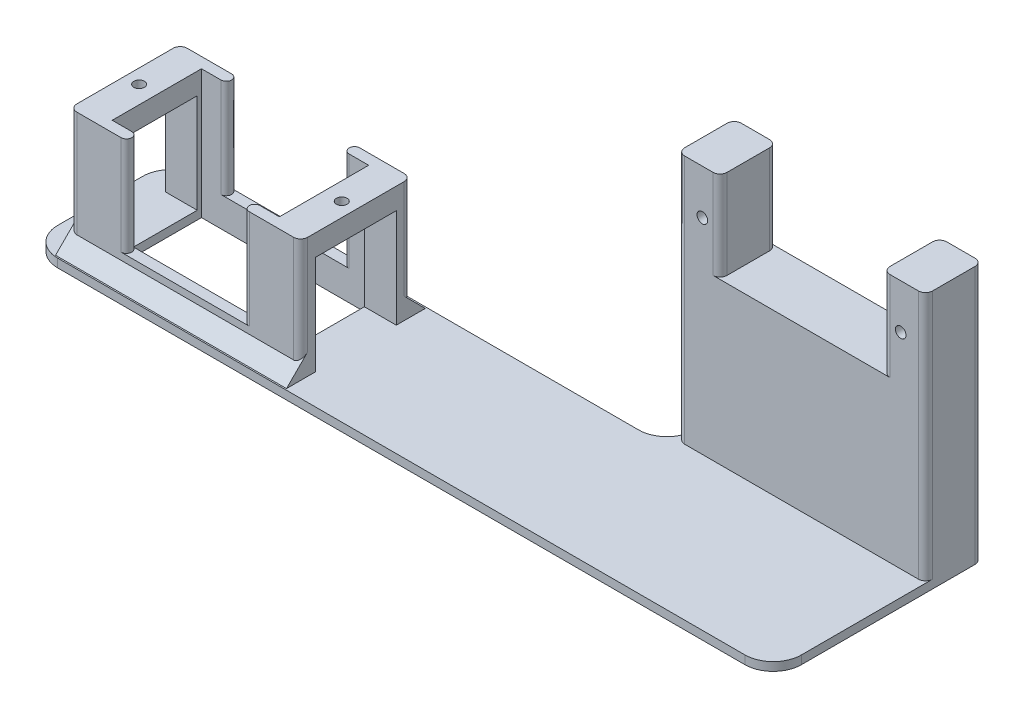
SolidWorks part; units mm, degrees
ref_plane "Plano frontal" through (0, 0, 0) normal (0, 0, 1) x (1, 0, 0)
ref_plane "Plano superior" through (0, 0, 0) normal (0, 1, 0) x (1, 0, 0)
ref_plane "Plano direito" through (0, 0, 0) normal (1, 0, 0) x (0, 0, -1)
sketch "Esboço1" plane through (0, 0, 0) normal (0, 1, 0) x (1, 0, 0)
  line L0 (-35.1312, 0) -> (39.0565, 0) construction
  line L1 (-52.5, -10) -> (52.5, -10)
  line L2 (-52.5, -10) -> (-52.5, 10)
  line L3 (-52.5, 10) -> (52.5, 10)
  line L4 (52.5, -10) -> (52.5, 10)
  line L5 (-52.5, -10) -> (52.5, 10) construction
  line L6 (-52.5, 10) -> (52.5, -10) construction
  line L8 (52.5, 10) -> (17.5, 10)
  line L9 (52.5, 10) -> (52.5, 19.5)
  line L10 (52.5, 19.5) -> (17.5, 19.5)
  line L11 (17.5, 10) -> (17.5, 19.5)
  point P0 (0, 0)
  dimension "D1" = 20
  dimension "D2" = 105
  dimension "D3" = 35
  dimension "D4" = 9.5
extrude "Base" add sketch "Esboço1" along normal blind 1.2 contours L11 L3 L9 L10 | L1 L4 L3 L2 region at (0, 0, 0) region at (35, 0, -14.75)
sketch "Esboço2" plane through (0, 1.2, 0) normal (0, 1, 0) x (1, 0, 0)
  line L0 (-51.7316, 0) -> (51.4564, 0) construction
  line L2 (-49, -7.8) -> (-16.4, -7.8)
  line L3 (-49, -7.8) -> (-49, 7.8)
  line L4 (-49, 7.8) -> (-16.4, 7.8)
  line L5 (-16.4, -7.8) -> (-16.4, 7.8)
  line L6 (-49, -7.8) -> (-16.4, 7.8) construction
  line L7 (-49, 7.8) -> (-16.4, -7.8) construction
  line L8 (-52.5, -10) -> (-52.5, 10) construction
  point P3 (-32.7, 0)
  dimension "D1" = 15.6
  dimension "D2" = 32.6
  dimension "D3" = 19.8
extrude "Suporte 1" add sketch "Esboço2" along normal blind 17 contours L4 L5 L2 L3
sketch "Esboço3" plane through (0, 18.2, 0) normal (0, 1, 0) x (1, 0, 0)
  line L0 (-41.688, 0) -> (-10.1812, 0) construction
  line L1 (-32.7, 8.1862) -> (-32.7, -8.1862) construction
  line L2 (-52.5, 10) -> (17.5, 10) construction
  line L3 (-44.5, -6.3) -> (-20.9, -6.3)
  line L4 (-44.5, -6.3) -> (-44.5, 6.3)
  line L5 (-44.5, 6.3) -> (-20.9, 6.3)
  line L6 (-20.9, -6.3) -> (-20.9, 6.3)
  line L7 (-44.5, -6.3) -> (-20.9, 6.3) construction
  line L8 (-44.5, 6.3) -> (-20.9, -6.3) construction
  line L9 (-52.5, -10) -> (-52.5, 10) construction
  point P5 (-32.7, 0)
  point P10 (0, 0)
  dimension "D1" = 23.6
  dimension "D2" = 12.6
  dimension "D3" = 10
  dimension "D4" = 19.8
extrude "Corte-extrusão1" cut sketch "Esboço3" against normal blind 19.5
sketch "Esboço4" plane through (0, 0, 7.8) normal (0, 0, 1) x (1, 0, 0)
  line L0 (-32.7, 25.969) -> (-32.7, -6.8255) construction
  line L1 (-52.5, 1.2) -> (-52.5, 0) construction
  line L3 (-41, 4.2) -> (-24.4, 4.2)
  line L4 (-41, 4.2) -> (-41, 21.4379)
  line L5 (-41, 21.4379) -> (-24.4, 21.4379)
  line L6 (-24.4, 4.2) -> (-24.4, 21.4379)
  line L7 (-41, 4.2) -> (-24.4, 21.4379) construction
  line L8 (-41, 21.4379) -> (-24.4, 4.2) construction
  line L10 (-49, 1.2) -> (-16.4, 1.2) construction
  point P4 (-32.7, 12.8189)
  dimension "D1" = 19.8
  dimension "D2" = 16.6
  dimension "D3" = 3
extrude "Corte-extrusão2" cut sketch "Esboço4" against normal blind 19.5
sketch "Esboço5" plane through (-16.4, 0, 0) normal (1, 0, 0) x (0, 0, -1)
  line L0 (0, 18.8039) -> (0, -2.4039) construction
  line L1 (-7.8, 1.2) -> (7.8, 1.2) construction
  line L2 (-5.7, 1.2) -> (5.7, 1.2)
  line L3 (-5.7, 1.2) -> (-5.7, 15.2)
  line L4 (-5.7, 15.2) -> (5.7, 15.2)
  line L5 (5.7, 1.2) -> (5.7, 15.2)
  line L6 (-5.7, 1.2) -> (5.7, 15.2) construction
  line L7 (-5.7, 15.2) -> (5.7, 1.2) construction
  line L8 (-7.8, 18.2) -> (7.8, 18.2) construction
  point P3 (0, 8.2)
  dimension "D1" = 11.4
  dimension "D2" = 0
  dimension "D3" = 3
extrude "Corte-extrusão3" cut sketch "Esboço5" against normal blind 36.5
sketch "Esboço6" plane through (0, 18.2, 0) normal (0, 1, 0) x (1, 0, 0)
  line L0 (-8.0264, 0) -> (-42.894, 0) construction
  line L3 (-16.4, -7.8) -> (-16.4, 7.8) construction
  line L4 (-49, -7.8) -> (-49, 7.8) construction
  circle A0 centre (-47, 0) radius 0.75
  circle A1 centre (-18.4, 0) radius 0.75
  dimension "D1" = 1.5
  dimension "D2" = 1.5
  dimension "D3" = 2
  dimension "D4" = 2
extrude "Corte-extrusão4" cut sketch "Esboço6" against normal blind 7.5
sketch "Esboço7" plane through (0, 1.2, 0) normal (0, 1, 0) x (1, 0, 0)
  line L0 (35, 27.9686) -> (35, -20.0329) construction
  line L1 (-55.355, 0) -> (59.9055, 0) construction
  line L2 (52.5, 19.5) -> (17.5, 19.5) construction
  line L3 (17.5, 19.5) -> (52.5, 19.5)
  line L4 (17.5, 19.5) -> (17.5, 11.5)
  line L5 (17.5, 11.5) -> (52.5, 11.5)
  line L6 (52.5, 19.5) -> (52.5, 11.5)
  line L7 (17.5, 19.5) -> (52.5, 11.5) construction
  line L8 (17.5, 11.5) -> (52.5, 19.5) construction
  point P5 (35, 15.5)
  point P12 (35, 19.5)
  dimension "D1" = 35
  dimension "D2" = 0
  dimension "D3" = 8
  dimension "D4" = 11.5
extrude "Ressalto-extrusão3" add sketch "Esboço7" along normal blind 35.24
sketch "Esboço9" plane through (0, 0, -11.5) normal (0, 0, 1) x (1, 0, 0)
  line L0 (35, 36.44) -> (35, -1.0136) construction
  line L1 (17.5, 36.44) -> (52.5, 36.44) construction
  line L3 (23.5, 49.04) -> (46.5, 49.04)
  line L4 (23.5, 49.04) -> (23.5, 23.84)
  line L5 (23.5, 23.84) -> (46.5, 23.84)
  line L6 (46.5, 49.04) -> (46.5, 23.84)
  line L7 (23.5, 49.04) -> (46.5, 23.84) construction
  line L8 (23.5, 23.84) -> (46.5, 49.04) construction
  point P4 (35, 36.44)
  dimension "D1" = 0
  dimension "D2" = 25.2
  dimension "D3" = 23
extrude "Corte-extrusão5" cut sketch "Esboço9" against normal blind 22.5
sketch "Esboço10" plane through (0, 0, -11.5) normal (0, 0, 1) x (1, 0, 0)
  line L0 (13.6486, 30.14) -> (51.3481, 30.14) construction
  line L1 (23.5, 36.44) -> (23.5, 23.84) construction
  line L2 (46.5, 23.84) -> (46.5, 36.44) construction
  circle A0 centre (21, 30.14) radius 0.75
  circle A1 centre (49, 30.14) radius 0.75
  dimension "D1" = 2.5
  dimension "D2" = 2.5
  dimension "D3" = 1.5
  dimension "D4" = 1.5
extrude "Corte-extrusão6" cut sketch "Esboço10" against normal blind 22.5
chamfer "Chanfro1" distance 2 angle 45 1 edges at (-32.7, 1.2, 7.8)
chamfer "Chanfro2" distance 2 angle 45 1 edges at (-32.7, 1.2, -7.8)
fillet "Filete1" radius 1 1 edges at (52.5, 18.22, -19.5) type face fillet first side face at (52.5, 12.5467, -7) second side face at (49.75, 30.14, -19.5)
fillet "Filete2" radius 1 1 edges at (17.5, 18.22, -19.5) type face fillet first side face at (49.75, 30.14, -19.5) second side face at (17.5, 12.5467, -13.6667)
fillet "Filete3" radius 1 1 edges at (23.5, 30.14, -19.5) type face fillet first side face at (23.5, 30.14, -15.5) second side face at (49.75, 30.14, -19.5)
fillet "Filete4" radius 1 1 edges at (46.5, 30.14, -19.5) type face fillet first side face at (46.5, 30.14, -15.5) second side face at (49.75, 30.14, -19.5)
fillet "Filete5" radius 1 1 edges at (52.5, 18.82, -11.5) type face fillet first side face at (49.75, 30.14, -11.5) second side face at (52.5, 12.5467, -6.6667)
fillet "Filete6" radius 1 1 edges at (17.5, 18.82, -11.5) type face fillet first side face at (17.5, 12.5467, -13.3333) second side face at (49.75, 30.14, -11.5)
fillet "Filete7" radius 1 1 edges at (46.5, 30.14, -11.5) type face fillet first side face at (46.5, 30.14, -15) second side face at (49.75, 30.14, -11.5)
fillet "Filete8" radius 1 1 edges at (23.5, 30.14, -11.5) type face fillet first side face at (49.75, 30.14, -11.5) second side face at (23.5, 30.14, -15)
fillet "Filete9" 2 edges at (-41, 11.2, 7.8) (-41, 11.2, 6.3) type full round first side face at (-32.7, 10.95, 7.8) second side face at (-32.7, 10.15, 6.3) middle face at (-41, 11.2, 7.05)
fillet "Filete10" 2 edges at (-41, 11.2, -7.8) (-41, 11.2, -6.3) type full round first side face at (-32.7, 10.95, -7.8) second side face at (-32.7, 10.15, -6.3) middle face at (-41, 11.2, -7.05)
fillet "Filete11" 2 edges at (-24.4, 11.2, 6.3) (-24.4, 11.2, 7.8) type full round first side face at (-32.8875, 10.15, 6.3) second side face at (-32.8875, 10.95, 7.8) middle face at (-24.4, 11.2, 7.05)
fillet "Filete12" 2 edges at (-24.4, 11.2, -7.8) (-24.4, 11.2, -6.3) type full round first side face at (-32.8875, 10.95, -7.8) second side face at (-32.8875, 10.15, -6.3) middle face at (-24.4, 11.2, -7.05)
fillet "Filete13" radius 1 1 edges at (-49, 10.7, -7.8) type face fillet first side face at (-32.7, 10.95, -7.8) second side face at (-49, 7.8, 0)
fillet "Filete14" radius 1 1 edges at (-49, 10.7, 7.8) type face fillet first side face at (-49, 7.9, 0.2) second side face at (-32.7, 10.95, 7.8)
fillet "Filete15" radius 1 1 edges at (-16.4, 10.7, 7.8) type face fillet first side face at (-32.45, 10.95, 7.8) second side face at (-16.4, 7.8, 0)
fillet "Filete16" radius 1 1 edges at (-16.4, 10.7, -7.8) type face fillet first side face at (-32.45, 10.95, -7.8) second side face at (-16.4, 7.9, -0.2)
fillet "Filete17" radius 4 1 edges at (-52.5, 0.6, 10) type face fillet first side face at (-52.5, 0.6, 0) second side face at (0, 0.6, 10)
fillet "Filete18" radius 4 1 edges at (-52.5, 0.6, -10) type face fillet first side face at (-17.5, 0.6, -10) second side face at (-52.5, 0.6, -2)
fillet "Filete19" radius 4 1 edges at (52.5, 0.6, 10) type face fillet first side face at (52.5, 12.5467, -7) second side face at (2, 0.6, 10)
fillet "Filete20" radius 4 1 edges at (17.5, 0.6, -10) type face fillet first side face at (17.5, 12.5467, -13.6667) second side face at (-15.5, 0.6, -10)
